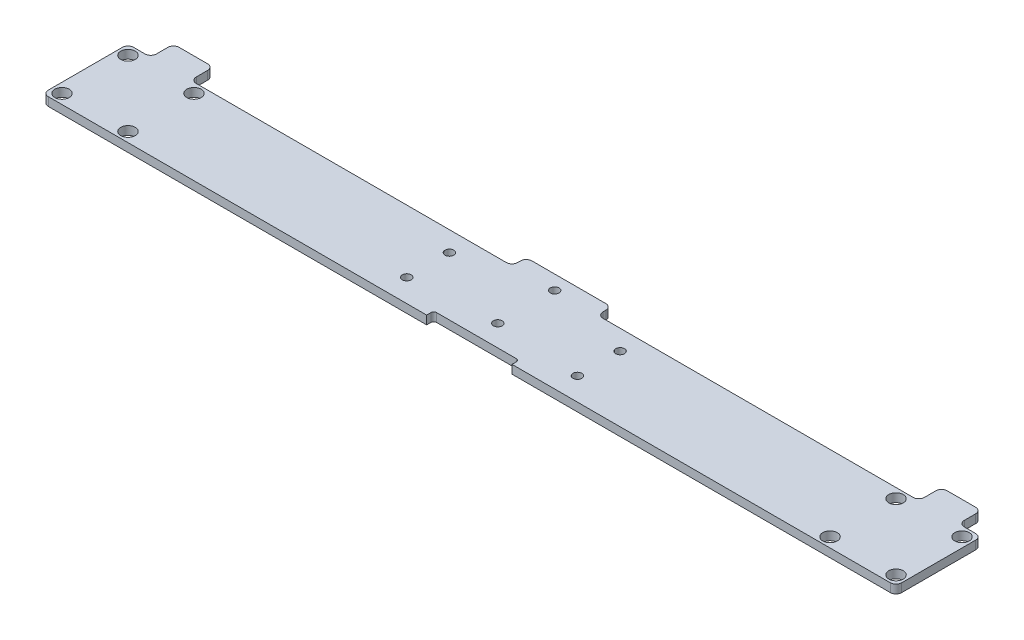
SolidWorks part; units mm, degrees
ref_plane "Alzado" through (0, 0, 0) normal (0, 0, 1) x (1, 0, 0)
ref_plane "Planta" through (0, 0, 0) normal (0, 1, 0) x (1, 0, 0)
ref_plane "Vista lateral" through (0, 0, 0) normal (1, 0, 0) x (0, 0, -1)
sketch "Croquis1" plane through (0, 0, 0) normal (0, 1, 0) x (1, 0, 0)
  line L0 (150, 30) -> (150, 0) construction
  line L1 (0, 0) -> (300, 0)
  line L2 (0, 0) -> (0, 30)
  line L3 (0, 30) -> (8, 30)
  line L4 (300, 0) -> (300, 30)
  line L5 (30, 30) -> (30, 0) construction
  line L6 (30, 30) -> (0, 0) construction
  line L7 (22, 30) -> (135, 30)
  line L8 (3.4, 3.4) -> (26.6, 3.4) construction
  line L9 (3.4, 3.4) -> (3.4, 26.6) construction
  line L10 (3.4, 26.6) -> (26.6, 26.6) construction
  line L11 (26.6, 3.4) -> (26.6, 26.6) construction
  line L12 (3.4, 3.4) -> (26.6, 26.6) construction
  line L13 (3.4, 26.6) -> (26.6, 3.4) construction
  line L15 (8, 30) -> (8, 38)
  line L16 (8, 38) -> (22, 38)
  line L17 (22, 30) -> (22, 38)
  line L18 (278, 30) -> (278, 38)
  line L19 (292, 38) -> (278, 38)
  line L20 (292, 30) -> (292, 38)
  line L21 (292, 30) -> (300, 30)
  line L22 (165, 30) -> (278, 30)
  line L24 (135, 30) -> (135, 35)
  line L25 (135, 35) -> (165, 35)
  line L26 (165, 30) -> (165, 35)
  circle A0 centre (3.4, 26.6) radius 2.55
  circle A1 centre (26.6, 26.6) radius 2.55
  circle A2 centre (26.6, 3.4) radius 2.55
  circle A3 centre (3.4, 3.4) radius 2.55
  circle A4 centre (273.4, 3.4) radius 2.55
  circle A5 centre (296.6, 3.4) radius 2.55
  circle A6 centre (296.6, 26.6) radius 2.55
  circle A7 centre (273.4, 26.6) radius 2.55
  circle A8 centre (150, 30) radius 1.55
  circle A9 centre (150, 10) radius 1.55
  circle A10 centre (120, 23) radius 1.55
  circle A11 centre (120, 8) radius 1.55
  circle A12 centre (180, 8) radius 1.55
  circle A13 centre (180, 23) radius 1.55
  point P9 (15, 15)
  dimension "D6" = 5.1
  dimension "D10" = 3.1
  dimension "D11" = 20
  dimension "D1" = 30
  dimension "D2" = 300
  dimension "D3" = 30
  dimension "D4" = 23.2
  dimension "D5" = 23.2
  dimension "D7" = 14
  dimension "D8" = 8
  dimension "D9" = 8
  dimension "D12" = 5
  dimension "D13" = 30
  dimension "D14" = 15
  dimension "D15" = 5
  dimension "D16" = 30
  dimension "D17" = 15
  dimension "D18" = 7
extrude "Saliente-Extruir1" add sketch "Croquis1" along normal blind 3
fillet "Redondeo2" radius 2 16 edges at (278, 1.5, -38) (292, 1.5, -38) (292, 1.5, -30) (22, 1.5, -30) (22, 1.5, -38) (8, 1.5, -30) (8, 1.5, -38) (0, 1.5, -30) (0, 1.5, 0) (300, 1.5, -30) (300, 1.5, 0) (135, 1.5, -30) (135, 1.5, -35) (165, 1.5, -35) (165, 1.5, -30) (278, 1.5, -30)
sketch "Croquis2" plane through (0, 3, 0) normal (0, 1, 0) x (1, 0, 0)
  line L0 (2, 0) -> (298, 0) construction
  line L1 (135, 0) -> (165, 0)
  line L2 (135, 0) -> (135, 1.5)
  line L3 (136, 2.5) -> (164, 2.5)
  line L4 (165, 0) -> (165, 1.5)
  line L5 (150, 0) -> (150, 23.6106) construction
  arc A1 (164, 2.5) -> (165, 1.5) centre (164, 1.5) cw
  arc A2 (135, 1.5) -> (136, 2.5) centre (136, 1.5) cw
  point P10 (165, 2.5)
  point P13 (135, 2.5)
  dimension "D4" = 1
  dimension "D1" = 30
  dimension "D2" = 2.5
  dimension "D3" = 15
extrude "Cortar-Extruir1" cut sketch "Croquis2" against normal up to surface (3 mm away) up to face at (180, 0, -9.55)
